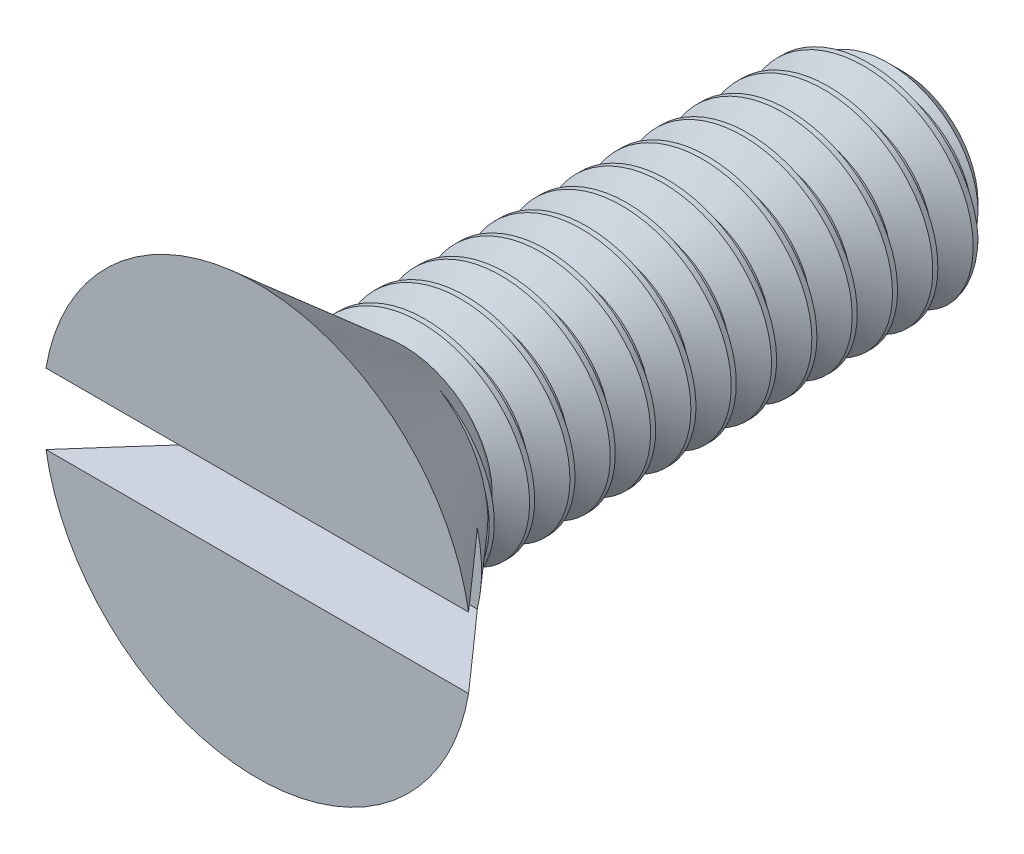
SolidWorks part; units mm, degrees
ref_plane "Front" through (0, 0, 0) normal (0, 0, 1) x (1, 0, 0)
ref_plane "Top" through (0, 0, 0) normal (0, 1, 0) x (1, 0, 0)
ref_plane "Right" through (0, 0, 0) normal (1, 0, 0) x (0, 0, -1)
sketch "Sketch1" plane through (0, 0, 0) normal (1, 0, 0) x (0, 0, -1)
  line L0 (-6.35, -4.2164) -> (-6.35, 4.2164) construction
  line L5 (-6.35, 4.2164) -> (-3.8956, 2.0828) construction
  line L6 (-3.8956, 2.0828) -> (6.35, 2.0828) construction
  line L7 (6.35, 2.0828) -> (6.35, -2.0828) construction
  line L8 (6.35, -2.0828) -> (-3.8956, -2.0828) construction
  line L9 (-3.8956, -2.0828) -> (-6.35, -4.2164) construction
  line L10 (-6.35, 0) -> (6.35, 0) construction
  line L11 (6.3004, 2.1687) -> (7.0941, 2.1687) construction
  line L12 (6.3004, 2.1687) -> (6.6973, 1.4813) construction
  line L13 (6.6973, 1.4813) -> (7.0941, 2.1687) construction
  line L14 (6.35, 2.0828) -> (7.0445, 2.0828) construction
  line L15 (6.6973, 2.0828) -> (6.6973, 2.1687) construction
  line L16 (6.3252, 2.1258) -> (7.0693, 2.1258) construction
  line L17 (6.6477, 1.5672) -> (6.7469, 1.5672) construction
  line L18 (6.6973, 1.5672) -> (6.6973, 1.4813) construction
  point P7 (-6.35, 0)
  point P8 (6.35, 0)
  point P9 (-3.81, 2.0828)
  point P11 (0, 0)
  point P14 (5.1594, -2.0828)
  point P24 (6.6973, 2.1258)
  dimension "Countersink Angle" = 82
  dimension "Length" = 12.7
  dimension "Screw Size Decimal Equivalent" = 4.1656
  dimension "Head Height" = 2.54
  dimension "Head Diameter" = 8.4328
  dimension "Thread Pitch" = 0.7937
  dimension "D1" = 0.0992
  dimension "D2" = 1.1906
sketch "Sketch2" plane through (0, 0, 0) normal (0, 0, 1) x (1, 0, 0)
  circle A0 centre (0, 0) radius 4.2164
  dimension "Head Dia" = 8.4328
sketch "Sketch4" plane through (0, 0, 0) normal (1, 0, 0) x (0, 0, -1)
  line L5 (-6.35, 4.2164) -> (-3.8956, 2.0828)
  line L10 (6.35, 0) -> (-6.35, 0)
  line L11 (-6.35, 0) -> (-6.35, 4.2164)
  line L12 (-3.8956, 2.0828) -> (6.35, 2.0828)
  line L13 (6.35, 2.0828) -> (6.35, 0)
revolve "Revolve1" add sketch "Sketch4" angle 360 about L10
sketch "Sketch13" plane through (0, 0, -6.35) normal (0, 0, -1) x (-1, 0, 0)
  circle A0 centre (0, 0) radius 2.0828 construction
  circle A2 centre (0, 0) radius 2.0828
chamfer "Chamfer1" distance 0.5953 angle 45 1 edges at (-2.0828, 0, -6.35)
ref_plane "Plane1" through (0, 0, 3.8956) normal (0, 0, 1) x (1, 0, 0)
split "Split1" trim tools "Plane1" bodies to split 112 resulting bodies 171 172
sketch "Sketch36" plane through (0, 0, 0) normal (1, 0, 0) x (0, 0, -1)
  line L0 (-6.35, 0.6943) -> (-4.826, 0.6943)
  line L1 (-4.826, 0.6943) -> (-4.826, -0.6943)
  line L2 (-4.826, -0.6943) -> (-6.35, -0.6943)
  line L3 (-6.35, -0.6943) -> (-6.35, 0.6943)
  line L4 (-6.35, -4.2164) -> (-6.35, 4.2164) construction
  line L5 (-6.35, 0) -> (6.35, 0) construction
  point P6 (-4.826, 0)
  dimension "D2" = 1.524
  dimension "D3" = 1.3885
extrude "Cut-Extrude1" cut sketch "Sketch36" against normal through all both and the other way through all
curve "Helix/Spiral1" pitch 0.7937 height 14.2875 turns 18
sketch "Sketch33" plane through (0, 0, 0) normal (1, 0, 0) x (0, 0, -1)
  line L0 (6.3252, 2.1258) -> (7.0693, 2.1258)
  line L1 (7.0693, 2.1258) -> (6.7469, 1.5672)
  line L2 (6.7469, 1.5672) -> (6.6477, 1.5672)
  line L3 (6.6477, 1.5672) -> (6.3252, 2.1258)
sweep "Cut-Sweep1" cut profiles "Sketch33" path "Helix/Spiral1"
sketch "Sketch35" plane through (0, 0, 0) normal (1, 0, 0) x (0, 0, -1)
  line L0 (-4.826, 2.8916) -> (-3.4215, 1.6707)
  line L1 (-6.35, 0) -> (6.35, 0) construction
  line L2 (-2.3117, 0) -> (-4.826, 0)
  line L3 (-4.826, 0) -> (-4.826, 2.8916)
  line L4 (-6.35, 4.2164) -> (-3.8956, 2.0828) construction
  line L6 (-3.1449, 1.5672) -> (-2.3117, 1.5672)
  line L7 (-2.3117, 1.5672) -> (-2.3117, 0)
  arc A0 (-3.1449, 1.5672) -> (-3.4215, 1.6707) centre (-3.1449, 1.9889) cw
  point P14 (-3.3025, 1.5672)
  dimension "D1" = 0.4216
  dimension "D2" = 0.8331
revolve "Revolve2" add sketch "Sketch35" angle 360 about L2
equation "\"D3@Helix/Spiral1\" = \"Length@Sketch1\" +  ( \"D4@Helix/Spiral1\" * 2 ) "
equation "\"D4@Helix/Spiral1\" = \"Thread Pitch@Sketch1\""
equation "\"D1@Sketch1\"=\"Thread Pitch@Sketch1\"/8"
equation "\"D1@Chamfer1\"=\"Thread Pitch@Sketch1\"*.75"
equation "\"D2@Sketch35\"=\"Screw Size Decimal Equivalent@Sketch1\"*.2"
equation "\"D2@Sketch36\"=\"Head Height@Sketch1\"*.6"
equation "\"D3@Sketch36\"=\"Screw Size Decimal Equivalent@Sketch1\"/3"
equation "\"D2@Sketch1\"=\"Thread Pitch@Sketch1\"*1.5"
equation "\"Head Dia@Sketch2\"= \"Head Diameter@Sketch1\""
equation "\"D1@Sketch35\"=\"Head Diameter@Sketch1\"*.05"
